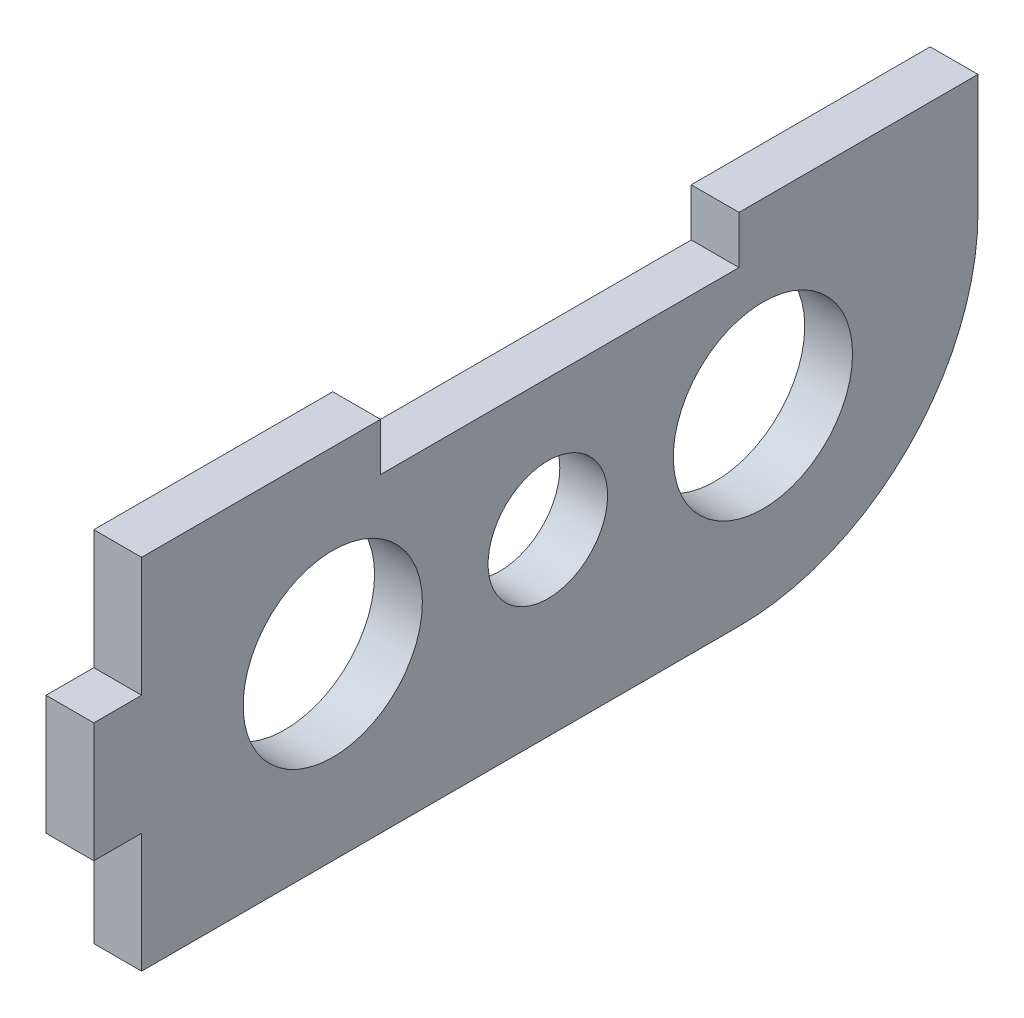
SolidWorks part; units mm, degrees
ref_plane "Front" through (0, 0, 0) normal (0, 0, 1) x (1, 0, 0)
ref_plane "Top" through (0, 0, 0) normal (0, 1, 0) x (1, 0, 0)
ref_plane "Right" through (0, 0, 0) normal (1, 0, 0) x (0, 0, -1)
sketch "Skizze1" plane through (0, 0, 0) normal (1, 0, 0) x (0, 0, -1)
  line L0 (0, 0) -> (74, 0) construction
  line L1 (0, -5) -> (0, 5)
  line L2 (0, 5) -> (4, 5)
  line L3 (4, 5) -> (4, 15)
  line L4 (4, 15) -> (74, 15)
  line L5 (74, 15) -> (74, -15)
  line L6 (4, -15) -> (74, -15)
  line L7 (4, -5) -> (4, -15)
  line L8 (0, -5) -> (4, -5)
  dimension "D1" = 4
  dimension "D2" = 10
  dimension "D3" = 30
  dimension "D4" = 70
extrude "Aufsatz-Linear austragen1" add sketch "Skizze1" along normal blind 4
sketch "Skizze2" [suppressed] plane through (4, 0, 0) normal (1, 0, 0) x (0, 0, -1)
  line L0 (39, 15) -> (39, 0) construction
  line L1 (4, 15) -> (24, 15)
  line L2 (4, 15) -> (4, 11)
  line L3 (4, 11) -> (24, 11)
  line L4 (24, 15) -> (24, 11)
  line L5 (74, 15) -> (54, 15)
  line L6 (74, 15) -> (74, 11)
  line L7 (74, 11) -> (54, 11)
  line L8 (54, 15) -> (54, 11)
  line L9 (74, 15) -> (4, 15) construction
  line L10 (39, 0) -> (0, 0) construction
  line L11 (54, -15) -> (54, -11)
  line L12 (74, -11) -> (54, -11)
  line L13 (74, -15) -> (74, -11)
  line L14 (74, -15) -> (54, -15)
  line L15 (24, -15) -> (24, -11)
  line L16 (4, -11) -> (24, -11)
  line L17 (4, -15) -> (4, -11)
  line L18 (4, -15) -> (24, -15)
  dimension "D1" = 4
  dimension "D2" = 30
extrude "Schnitt-Linear austragen1" [suppressed] cut sketch "Skizze2" against normal through all
sketch "Skizze3" plane through (4, 0, 0) normal (1, 0, 0) x (0, 0, -1)
  line L0 (74, 15) -> (4, 15) construction
  line L1 (24, 15) -> (54, 15)
  line L2 (24, 15) -> (24, 11)
  line L3 (24, 11) -> (54, 11)
  line L4 (54, 15) -> (54, 11)
  line L5 (39, -15) -> (39, 11) construction
  line L6 (4, -15) -> (74, -15) construction
  dimension "D1" = 4
  dimension "D2" = 30
extrude "Schnitt-Linear austragen2" cut sketch "Skizze3" against normal through all
sketch "Skizze4" [suppressed] plane through (4, 0, 0) normal (1, 0, 0) x (0, 0, -1)
  line L0 (0, 0) -> (36, 0) construction
  line L1 (41, 10) -> (31, 10) construction
  line L2 (41, 10) -> (41, -10) construction
  line L3 (41, -10) -> (31, -10) construction
  line L4 (31, 10) -> (31, -10) construction
  line L5 (41, 10) -> (31, -10) construction
  line L6 (41, -10) -> (31, 10) construction
  line L7 (0, 5) -> (0, -5) construction
  circle A0 centre (41, 10) radius 1.55
  circle A1 centre (31, 10) radius 1.55
  circle A2 centre (31, -10) radius 1.55
  circle A3 centre (41, -10) radius 1.55
  point P0 (36, 0)
  dimension "D3" = 3.1
  dimension "D1" = 10
  dimension "D2" = 20
  dimension "D4" = 36
extrude "Schnitt-Linear austragen3" [suppressed] cut sketch "Skizze4" against normal blind 10
fillet "Verrundung1" radius 20 1 edges at (2, -15, -74)
sketch "Skizze5" plane through (4, 0, 0) normal (1, 0, 0) x (0, 0, -1)
  line L0 (20, 0) -> (38, 0) construction
  line L1 (38, 0) -> (56, 0) construction
  line L2 (0, 5) -> (0, -5) construction
  line L3 (0, 0) -> (20, 0) construction
  circle A0 centre (20, 0) radius 7.5
  circle A1 centre (56, 0) radius 7.5
  circle A2 centre (38, 0) radius 5
  dimension "D1" = 15
  dimension "D2" = 10
  dimension "D3" = 18
  dimension "D4" = 20
extrude "Schnitt-Linear austragen4" cut sketch "Skizze5" against normal through all
